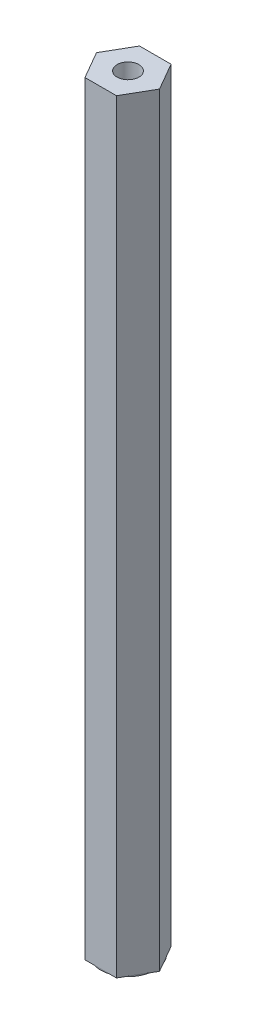
SolidWorks part; units mm, degrees
material "6063-T6"
ref_plane "Front" through (0, 0, 0) normal (0, 0, 1) x (1, 0, 0)
ref_plane "Top" through (0, 0, 0) normal (0, 1, 0) x (1, 0, 0)
ref_plane "Right" through (0, 0, 0) normal (1, 0, 0) x (0, 0, -1)
sketch "Sketch1" plane through (0, 0, 0) normal (0, 1, 0) x (1, 0, 0)
  line L1 (7.3323, 0) -> (3.6662, 6.35)
  line L2 (3.6662, 6.35) -> (-3.6662, 6.35)
  line L3 (-3.6662, 6.35) -> (-7.3323, 0)
  line L4 (-7.3323, 0) -> (-3.6662, -6.35)
  line L5 (-3.6662, -6.35) -> (3.6662, -6.35)
  line L6 (3.6662, -6.35) -> (7.3323, 0)
  circle A0 centre (0, 0) radius 6.35 construction
extrude "Boss-Extrude1" add sketch "Sketch1" along normal blind 177.8
sketch "Sketch2" plane through (0, 177.8, 0) normal (0, 1, 0) x (1, 0, 0)
  circle A0 centre (0, 0) radius 2.54
  dimension "D1" = 5.08
extrude "Cut-Extrude1" cut sketch "Sketch2" against normal blind 25.4
sketch "Sketch3" plane through (0, 0, 0) normal (0, -1, 0) x (1, 0, 0)
  circle A0 centre (0, 0) radius 6.35
extrude "Boss-Extrude2" add sketch "Sketch3" along normal blind 0.254
